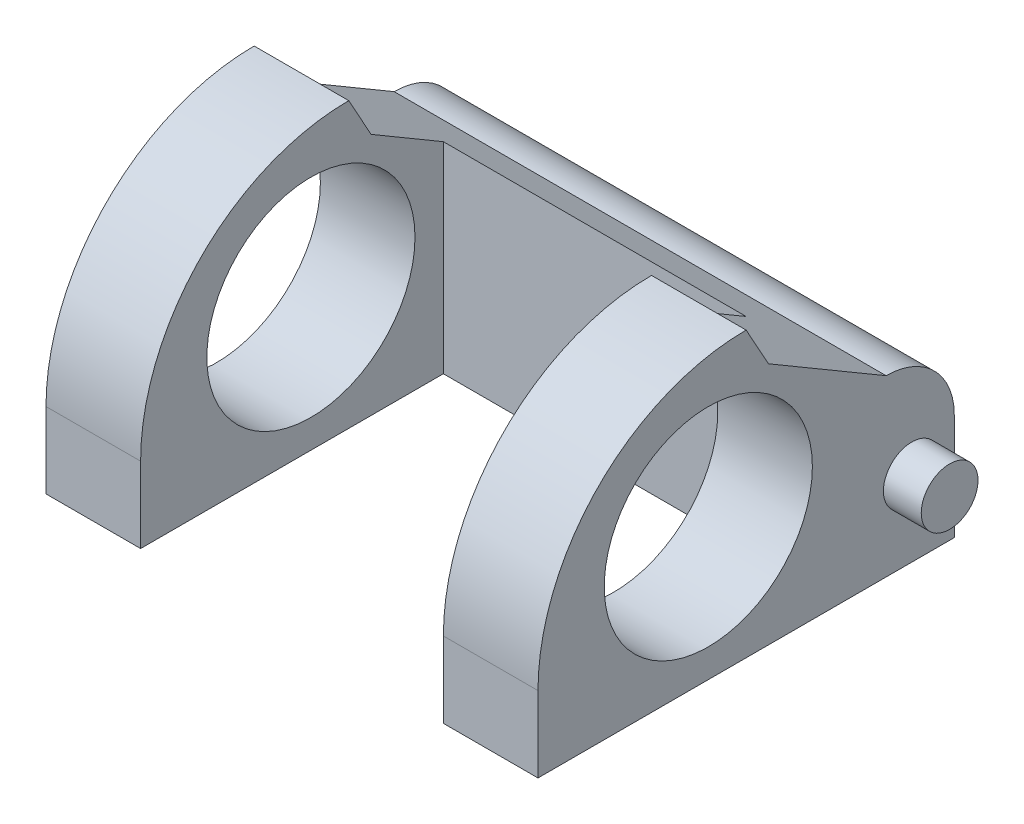
SolidWorks part; units mm, degrees
ref_plane "前视基准面" through (0, 0, 0) normal (0, 0, 1) x (1, 0, 0)
ref_plane "上视基准面" through (0, 0, 0) normal (0, 1, 0) x (1, 0, 0)
ref_plane "右视基准面" through (0, 0, 0) normal (1, 0, 0) x (0, 0, -1)
sketch "草图3" plane through (0, 0, 0) normal (0, 1, 0) x (1, 0, 0)
  line L1 (-6.5, 5.5) -> (6.5, 5.5)
  line L2 (-6.5, 5.5) -> (-6.5, -5.5)
  line L3 (-6.5, -5.5) -> (6.5, -5.5)
  line L4 (6.5, 5.5) -> (6.5, -5.5)
  line L5 (-6.5, 5.5) -> (6.5, -5.5) construction
  line L6 (-6.5, -5.5) -> (6.5, 5.5) construction
  point P0 (0, 0)
  dimension "D1" = 13
  dimension "D2" = 11
extrude "凸台-拉伸1" add sketch "草图3" along normal blind 10
sketch "草图5" plane through (6.5, 0, 0) normal (1, 0, 0) x (0, 0, -1)
  line L0 (-5.5, 0) -> (-5.5, 2)
  line L1 (-5.5, 10) -> (-5.5, 0) construction
  line L2 (-5.5, 2) -> (-3.3049, 2) construction
  line L3 (5.5, 10) -> (5.5, 0) construction
  line L4 (0, 7.5) -> (0.5904, 6.4329)
  line L5 (0.5904, 6.4329) -> (3.699, 4.6064)
  line L6 (5.5, 2.8054) -> (5.5, 0)
  line L7 (-5.5, 0) -> (5.5, 0)
  line L8 (-5.5, 2) -> (-5.5, 10)
  line L9 (-5.5, 10) -> (5.5, 10)
  line L10 (5.5, 10) -> (5.5, 2.8054)
  line L11 (1.3049, 2) -> (5.5, 2) construction
  arc A2 (0, 7.5) -> (-5.5, 2) centre (0, 2) ccw
  arc A3 (5.5, 2.8054) -> (3.699, 4.6064) centre (3.699, 2.8054) ccw
  circle A4 centre (-1, 3.5) radius 2.75
  circle A5 centre (4.3764, 2) radius 0.75
  line M4 (5.5, 0) -> (5.5, 10)
  line M5 (5.5, 10) -> (-5.5, 10)
  line M6 (-5.5, 10) -> (-5.5, 0)
  dimension "D1" = 6.5
  dimension "D2" = 5.5
  dimension "D5" = 1.5
  dimension "D3" = 2
  dimension "D4" = 3.5
extrude "切除-拉伸3" cut sketch "草图5" against normal through all contours A4 | A3 A2 L4 L5 M4 M5 M6 region at (6.5, 7.7141, -0.3146) region at (6.5, 3.5, 1)
extrude "凸台-拉伸2" add sketch "草图5<6>" along normal blind 1 contours A5
sketch "草图5<6>" plane through (6.5, 0, 0) normal (1, 0, 0) x (0, 0, -1) same geometry as "草图5"
sketch "草图10" plane through (0, 0, 0) normal (0, -1, 0) x (1, 0, 0)
  line L0 (3.5, 5.5) -> (3.5, -2.5)
  line L1 (-6.5, 5.5) -> (6.5, 5.5) construction
  line L2 (3.5, -2.5) -> (-3.5, -2.5)
  line L3 (-3.5, -2.5) -> (-3.5, 5.5)
  line L4 (6.5, 5.5) -> (6.5, -5.5) construction
  line L5 (-6.5, -5.5) -> (-6.5, 5.5) construction
  line L6 (6.5, -5.5) -> (-6.5, -5.5) construction
  line L7 (3.5, 5.5) -> (-3.5, 5.5)
  dimension "D1" = 3
  dimension "D2" = 3
  dimension "D3" = 3
extrude "切除-拉伸5" cut sketch "草图10" against normal through all
mirror "镜向1" about plane through (0, 0, 0) normal (1, 0, 0) of "凸台-拉伸2"
sketch "草图11" plane through (0, 0, 0) normal (0, -1, 0) x (-1, 0, 0)
  line L0 (-4, -5.5) -> (-4, 2.5)
  line L3 (-3.5, -5.5) -> (-6.5, -5.5) construction
  line L4 (4, -5.5) -> (4, 2.5)
  line L5 (6.5, -5.5) -> (3.5, -5.5) construction
  line L6 (4, 2.5) -> (3.5, 2.5)
  line L7 (-4, 2.5) -> (-3.5, 2.5)
  line L8 (3.5, -5.5) -> (3.5, 2.5) construction
  line L9 (-3.5, 2.5) -> (-3.5, -5.5) construction
  line L10 (-3.5, -5.5) -> (-4, -5.5)
  line L11 (4, -5.5) -> (3.5, -5.5)
  line L12 (3.5, -5.5) -> (3.5, 2.5)
  line L13 (-3.5, 2.5) -> (-3.5, -5.5)
  dimension "D1" = 0.5
  dimension "D2" = 0.5
extrude "切除-拉伸6" cut sketch "草图11" against normal through all
